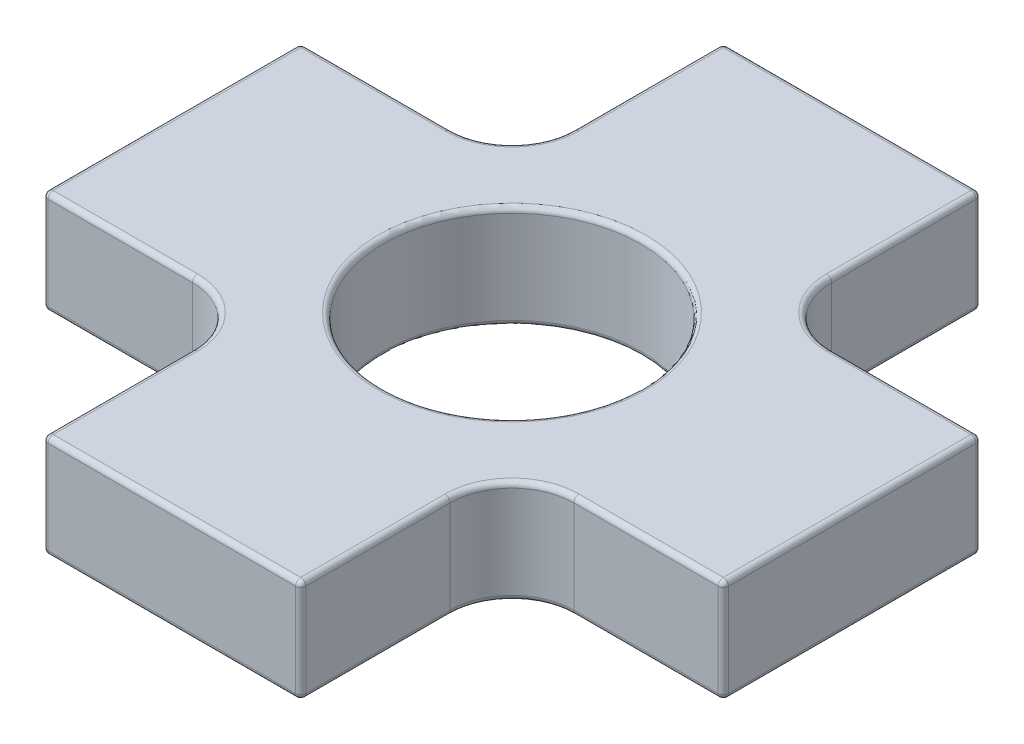
SolidWorks part; units mm, degrees
ref_plane "前视基准面" through (0, 0, 0) normal (0, 0, 1) x (1, 0, 0)
ref_plane "上视基准面" through (0, 0, 0) normal (0, 1, 0) x (1, 0, 0)
ref_plane "右视基准面" through (0, 0, 0) normal (1, 0, 0) x (0, 0, -1)
sketch "草图1" plane through (0, 0, 0) normal (0, 1, 0) x (1, 0, 0)
  line L0 (6.25, 6.25) -> (16.5, 6.25)
  line L1 (-6.25, -16.5) -> (6.25, -16.5)
  line L2 (-6.25, -16.5) -> (-6.25, -6.25)
  line L3 (-6.25, 16.5) -> (6.25, 16.5)
  line L4 (6.25, -16.5) -> (6.25, -6.25)
  line L5 (-6.25, -16.5) -> (6.25, 16.5) construction
  line L6 (-6.25, 16.5) -> (6.25, -16.5) construction
  line L7 (-16.5, -6.25) -> (-6.25, -6.25)
  line L8 (-16.5, -6.25) -> (-16.5, 6.25)
  line L9 (-16.5, 6.25) -> (-6.25, 6.25)
  line L10 (16.5, -6.25) -> (16.5, 6.25)
  line L11 (-16.5, -6.25) -> (16.5, 6.25) construction
  line L12 (-16.5, 6.25) -> (16.5, -6.25) construction
  line L13 (-6.25, 6.25) -> (-6.25, 16.5)
  line L14 (6.25, -6.25) -> (16.5, -6.25)
  line L15 (6.25, 6.25) -> (6.25, 16.5)
  point P0 (0, 0)
  point P6 (0, 0)
  dimension "D1" = 12.5
  dimension "D2" = 33
extrude "凸台-拉伸1" add sketch "草图1" along normal blind 5
sketch "草图2" plane through (0, 5, 0) normal (0, 1, 0) x (1, 0, 0)
  circle A0 centre (0, 0) radius 6.25
  dimension "D1" = 12.5
extrude "切除-拉伸1" cut sketch "草图2" against normal blind 5
fillet "圆角1" radius 3 4 edges at (6.25, 2.5, 6.25) (-6.25, 2.5, 6.25) (-6.25, 2.5, -6.25) (6.25, 2.5, -6.25)
fillet "圆角2" radius 0.25 34 edges at (0, 0, -16.5) (-6.25, 0, -12.875) (-7.1287, 0, -7.1287) (-12.875, 0, -6.25) (-16.5, 0, 0) (-12.875, 0, 6.25) (-7.1287, 0, 7.1287) (-6.25, 0, 12.875) (0, 0, 16.5) (6.25, 0, 12.875) (7.1287, 0, 7.1287) (12.875, 0, 6.25) (16.5, 0, 0) (12.875, 0, -6.25) (7.1287, 0, -7.1287) (6.25, 0, -12.875) (0, 0, 6.25) (16.5, 5, 0) (12.875, 5, 6.25) (7.1287, 5, 7.1287) (6.25, 5, 12.875) (0, 5, 16.5) (-6.25, 5, 12.875) (-7.1287, 5, 7.1287) (-12.875, 5, 6.25) (-16.5, 5, 0) (-12.875, 5, -6.25) (-7.1287, 5, -7.1287) (-6.25, 5, -12.875) (0, 5, -16.5) (6.25, 5, -12.875) (7.1287, 5, -7.1287) (12.875, 5, -6.25) (0, 5, 6.25)
fillet "圆角3" radius 0.25 24 edges at (-6.1768, 4.9268, -16.4268) (-6.1768, 0.0732, -16.4268) (6.1768, 4.9268, -16.4268) (6.1768, 0.0732, -16.4268) (16.4268, 4.9268, 6.1768) (16.4268, 0.0732, 6.1768) (16.4268, 4.9268, -6.1768) (16.4268, 0.0732, -6.1768) (-6.1768, 4.9268, 16.4268) (-6.1768, 0.0732, 16.4268) (6.1768, 4.9268, 16.4268) (6.1768, 0.0732, 16.4268) (-16.4268, 4.9268, -6.1768) (-16.4268, 0.0732, -6.1768) (-16.4268, 4.9268, 6.1768) (-16.4268, 0.0732, 6.1768) (-6.25, 2.5, -16.5) (6.25, 2.5, -16.5) (16.5, 2.5, 6.25) (16.5, 2.5, -6.25) (-6.25, 2.5, 16.5) (6.25, 2.5, 16.5) (-16.5, 2.5, -6.25) (-16.5, 2.5, 6.25)
